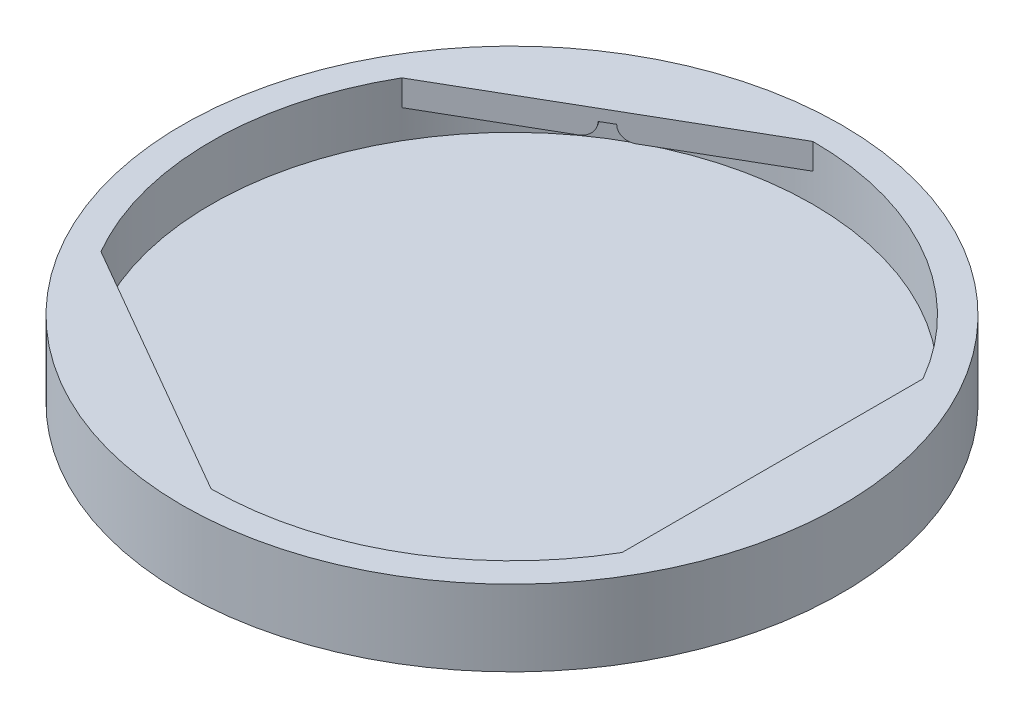
SolidWorks part; units mm, degrees
ref_plane "Front" through (0, 0, 0) normal (0, 0, 1) x (1, 0, 0)
ref_plane "Top" through (0, 0, 0) normal (0, 1, 0) x (1, 0, 0)
ref_plane "Right" through (0, 0, 0) normal (1, 0, 0) x (0, 0, -1)
sketch "Sketch1" plane through (0, 0, 0) normal (0, 1, 0) x (1, 0, 0)
  circle A0 centre (0, 0) radius 23
extrude "Boss-Extrude1" add sketch "Sketch1" along normal blind 1.5
sketch "Sketch2" plane through (0, 1.5, 0) normal (0, 1, 0) x (1, 0, 0)
  circle A0 centre (0, 0) radius 23
  circle A1 centre (0, 0) radius 21
extrude "Boss-Extrude2" add sketch "Sketch2" along normal blind 2
sketch "Sketch3" plane through (0, 3.5, 0) normal (0, 1, 0) x (1, 0, 0)
  line L6 (-18.1865, 10.5) -> (0, 21)
  line L7 (18.1865, 10.5) -> (18.1865, -10.5)
  line L8 (-18.1865, -10.5) -> (0, -21)
  circle A0 centre (0, 0) radius 23
  arc A1 (-18.1865, 10.5) -> (-18.1865, -10.5) centre (0, 0) ccw
  arc A2 (18.1865, 10.5) -> (0, 21) centre (0, 0) ccw
  arc A3 (0, -21) -> (18.1865, -10.5) centre (0, 0) ccw
  point P12 (0, 0)
extrude "Boss-Extrude3" add sketch "Sketch3" along normal blind 1.8
ref_plane "Plane1" through (0, 3.5, 0) normal (0, 1, 0) x (1, 0, 0)
sketch "Sketch4" plane through (0, 3.5, 0) normal (0, 1, 0) x (1, 0, 0)
  line L0 (0, 0) -> (-9.0933, 15.75) construction
  line L1 (0, 21) -> (-18.1865, 10.5) construction
  line L2 (-9.405, 15.3475) -> (-11.7562, 19.1844)
  line L3 (-8.5889, 15.8187) -> (-10.7361, 19.7734)
  arc A0 (-10.7361, 19.7734) -> (-11.7562, 19.1844) centre (0, 0) ccw
  arc A1 (-8.5889, 15.8187) -> (-9.405, 15.3475) centre (0, 0) ccw
  point P3 (0, 0)
  dimension "D1" = 1.5
extrude "Cut-Extrude1" cut sketch "Sketch4" along normal blind 1
fillet "Fillet2" radius 1 2 edges at (-9.3506, 3.5, -17.2216) (-10.2391, 3.5, -16.7087) first distance on face at (-9.7708, 3.9, -17.9956) first distance on face at (-10.6993, 3.9, -17.4596)
pattern_circular "CirPattern1" count 3 over 360 about axis through (0, 5.3, 0) along (0, 1, 0) of "Cut-Extrude1", "Fillet2"
